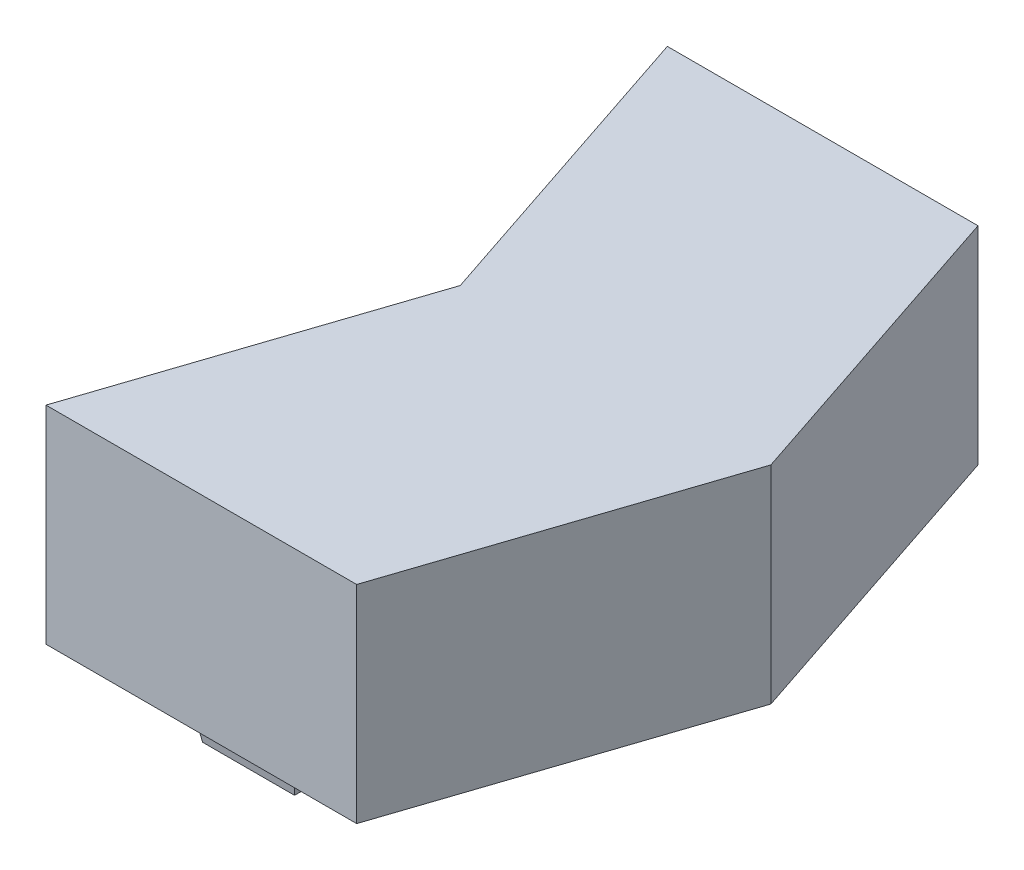
SolidWorks part; units mm, degrees
ref_plane "Front Plane" through (0, 0, 0) normal (0, 0, 1) x (1, 0, 0)
ref_plane "Top Plane" through (0, 0, 0) normal (0, 1, 0) x (1, 0, 0)
ref_plane "Right Plane" through (0, 0, 0) normal (1, 0, 0) x (0, 0, -1)
sketch "Sketch1" plane through (0, 0, 0) normal (0, 1, 0) x (1, 0, 0)
  line L0 (0, 0) -> (19.05, 0)
  line L1 (19.05, 0) -> (25.4, 19.05)
  line L2 (25.4, 19.05) -> (19.05, 38.1)
  line L3 (19.05, 38.1) -> (0, 38.1)
  line L4 (0, 38.1) -> (6.35, 19.05)
  line L5 (6.35, 19.05) -> (0, 0)
  dimension "D1" = 19.05
  dimension "D2" = 38.1
  dimension "D3" = 6.35
  dimension "D5" = 19.05
extrude "Boss-Extrude1" add sketch "Sketch1" along normal blind 12.7
sketch "Sketch2" plane through (0, 0, 0) normal (0, -1, 0) x (1, 0, 0)
  line L0 (25.4, -19.05) -> (6.35, -19.05) construction
  line L1 (6.35, -19.05) -> (0, 0) construction
  circle A0 centre (15.24, -19.05) radius 5.635
  dimension "D1" = 11.27
  dimension "D2" = 8.89
extrude "Haptic Motor Cutout" cut sketch "Sketch2" against normal blind 9.558 contours A0
sketch "Sketch3" plane through (0, 0, 0) normal (0, -1, 0) x (1, 0, 0)
  line L8 (16.51, -24.54) -> (13.97, -24.54)
  line L9 (16.51, -24.54) -> (16.51, -28.35)
  line L10 (13.97, -24.54) -> (13.97, -28.35)
  line L11 (16.51, -28.35) -> (13.97, -28.35)
  circle A3 centre (15.24, -19.05) radius 5.635 construction
  dimension "D1" = 2.54
  dimension "D2" = 3.81
extrude "Haptic Wire Cutout" cut sketch "Sketch3" against normal blind 9.558
ref_plane "MidPlane" through (0, 0, -19.05) normal (0, 0, -1) x (-1, 0, 0)
sketch "Sketch4" plane through (0, 0, 0) normal (0, -1, 0) x (1, 0, 0)
  line L0 (19.05, -38.1) -> (0, -38.1) construction
  line L1 (13.97, -36.83) -> (7.62, -36.83)
  line L2 (13.97, -36.83) -> (13.97, -34.29)
  line L3 (13.97, -34.29) -> (7.62, -34.29)
  line L4 (7.62, -36.83) -> (7.62, -34.29)
  line L5 (0, -6.985) -> (0, 6.985) construction
  dimension "D1" = 2.54
  dimension "D2" = 6.35
  dimension "D3" = 1.27
  dimension "D4" = 7.62
extrude "Pins" add sketch "Sketch4" along normal blind 2.032 draft 10
mirror "Mirror1" about plane through (0, 0, -19.05) normal (0, 0, -1) of "Pins"
ref_point "Point1"
ref_axis "Axis1" through (0, 12.7, -38.1) along (0, 0, 1)
sketch "Sketch5" plane through (0, 12.7, 0) normal (0, 1, 0) x (1, 0, 0)
  line L0 (0, 38.1) -> (0, 0) construction
  line L1 (0, 19.05) -> (25.4, 19.05) construction
equation "\"Arrow Height\"= 1.5in"
equation "\"Button Height\"= 2in"
equation "\"Button Width\"= 4in"
equation "\"Haptic Diameter\"= 10mm"
equation "\"Haptic Thickness\"= 2.7mm"
equation "\"D2@Sketch1\"=\"Arrow Height\""
equation "\"D5@Sketch1\"=\"Arrow Height\"/2"
equation "\"D1@Sketch2\"=\"Haptic Diameter\"+.05in"
equation "\"D1@Haptic Motor Cutout\"=\"Haptic Thickness\" + .02+.25"
equation "\"D1@Haptic Wire Cutout\"=\"Haptic Thickness\"+.02+.25"
equation "\"Arrow Spacing\"= 1in"
equation "\"Arrow Width\"= 01in"
equation "\"Haptic Wire Angle\"= 63.43"
equation "\"Haptic Wire Width\"= .1in"
equation "\"Haptic Wire Height\"= .15in"
